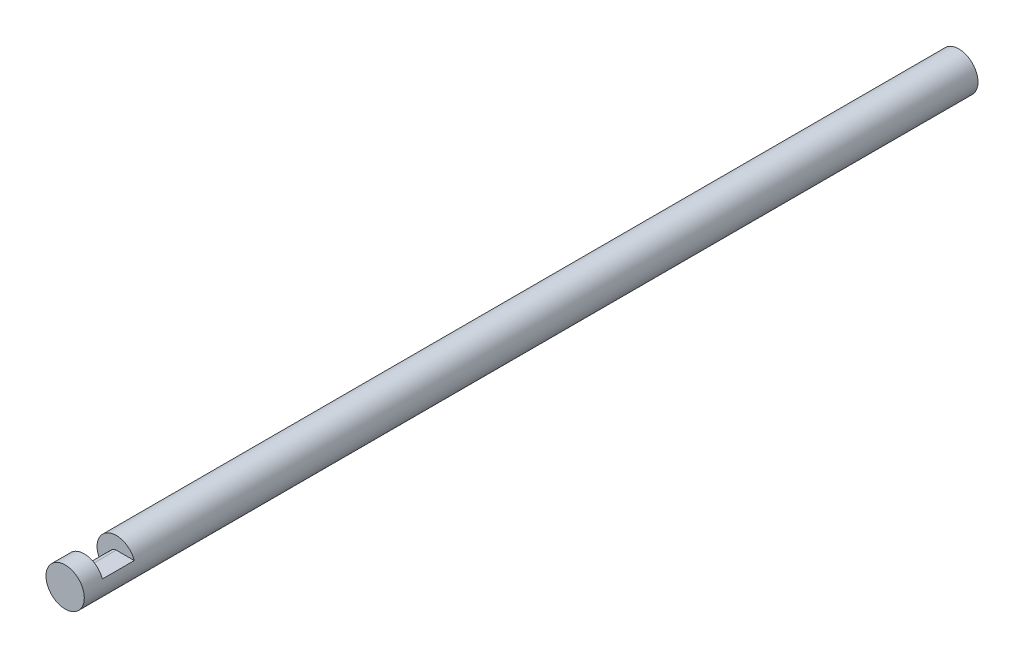
SolidWorks part; units mm, degrees
material "AISI 316 Annealed Stainless Steel Bar (SS)"
ref_plane "Front" through (0, 0, 0) normal (0, 0, 1) x (1, 0, 0)
ref_plane "Top" through (0, 0, 0) normal (0, 1, 0) x (1, 0, 0)
ref_plane "Right" through (0, 0, 0) normal (1, 0, 0) x (0, 0, -1)
ref_axis "X" through (-80.9, 0, 0) along (1, 0, 0)
ref_axis "Y" through (0, -50, 0) along (0, 1, 0)
ref_axis "Z" through (0, 0, -80.9) along (0, 0, 1)
sketch "Sketch1" plane through (0, 0, 0) normal (1, 0, 0) x (0, 0, -1)
  line L0 (0, 0) -> (0, 1.5)
  line L1 (0, 1.5) -> (70, 1.5)
  line L2 (70, 1.5) -> (70, 0)
  line L3 (70, 0) -> (0, 0)
  line L4 (-9.841, 0) -> (-3.2015, 0) construction
  dimension "D1" = 3
  dimension "D2" = 70
revolve "Revolve1" add sketch "Sketch1" angle 360 about L4
sketch "Sketch2" plane through (0, 0, 0) normal (0, 0, 1) x (1, 0, 0)
  line L0 (0, 0.5) -> (1.4142, 0.5)
  line L1 (-0.5, 0) -> (-0.5, -1.4142)
  arc A0 (0, 0.5) -> (-0.5, 0) centre (0, 0) ccw
  circle A2 centre (0, 0) radius 1.5
  arc A3 (1.4142, 0.5) -> (-0.5, -1.4142) centre (0, 0) ccw
  dimension "D2" = 0.5
  dimension "D1" = 0
extrude "Cut-Extrude1" cut sketch "Sketch2" against normal blind 2.5 from offset 1.5 offset against normal yes
